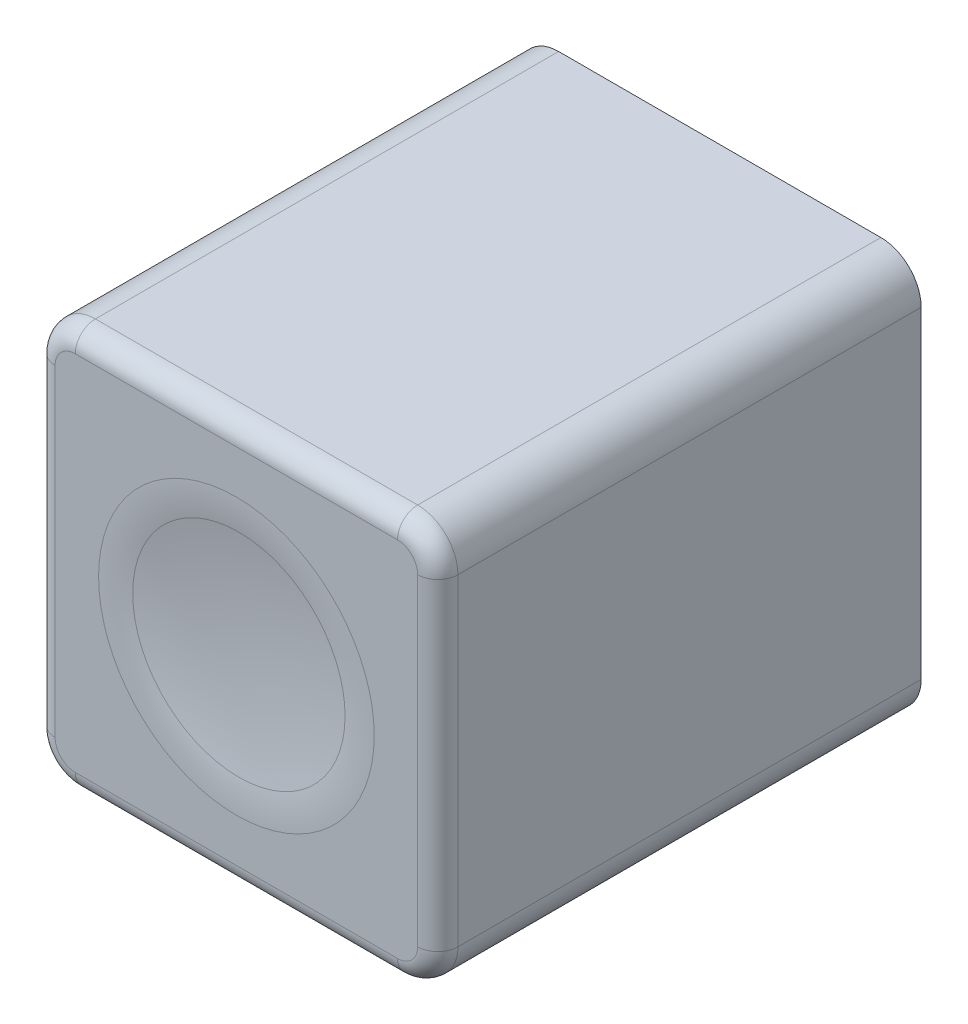
SolidWorks part; units mm, degrees
ref_plane "Спереди" through (0, 0, 0) normal (0, 0, 1) x (1, 0, 0)
ref_plane "Сверху" through (0, 0, 0) normal (0, 1, 0) x (1, 0, 0)
ref_plane "Справа" through (0, 0, 0) normal (1, 0, 0) x (0, 0, -1)
ref_plane "Плоскость1" through (0, 0, -3) normal (0, 0, 1) x (1, 0, 0)
sketch "Эскиз1" plane through (0, 0, -3) normal (0, 0, 1) x (1, 0, 0)
  line L0 (-5, 5) -> (5, 5) construction
  line L1 (-5, 5) -> (-5, -5) construction
  line L2 (-5, -5) -> (5, -5) construction
  line L3 (5, 5) -> (5, -5) construction
  line L4 (-5, 5) -> (5, 5)
  line L5 (-5, 5) -> (-5, -5)
  line L6 (-5, -5) -> (5, -5)
  line L7 (5, 5) -> (5, -5)
extrude "Бобышка-Вытянуть1" add sketch "Эскиз1" along normal blind 5 and the other way blind 7
fillet "Скругление1" radius 1 4 edges at (5, -5, -4) (-5, -5, -4) (-5, 5, -4) (5, 5, -4)
fillet "Скругление2" radius 0.5 8 edges at (-4.7071, -4.7071, 2) (-5, 0, 2) (-4.7071, 4.7071, 2) (0, 5, 2) (4.7071, 4.7071, 2) (5, 0, 2) (4.7071, -4.7071, 2) (0, -5, 2)
sketch "Эскиз2" plane through (0, 0, 0) normal (1, 0, 0) x (0, 0, -1)
  line L0 (-2, -4) -> (-2, 4) construction
  line L1 (-1.5, 5) -> (10, 5) construction
  line L2 (10, -5) -> (-1.5, -5) construction
  line L3 (-2, 3) -> (-2, -3)
  line L4 (0, 0) -> (-3.8705, 0) construction
  line L5 (-2, 0) -> (-1.7295, 0)
  arc A0 (-2, 3) -> (-2, -3) centre (-18.5, 0) cw
  dimension "D1" = 2
  dimension "D2" = 2
  dimension "D3" = 16.5
revolve "Вырез-Повернуть2" cut sketch "Эскиз2" angle 360 about L4 region at (0, 1.1262, 1.8917)
fillet "Скругление3" radius 5 1 edges at (-3, 0, 2)
